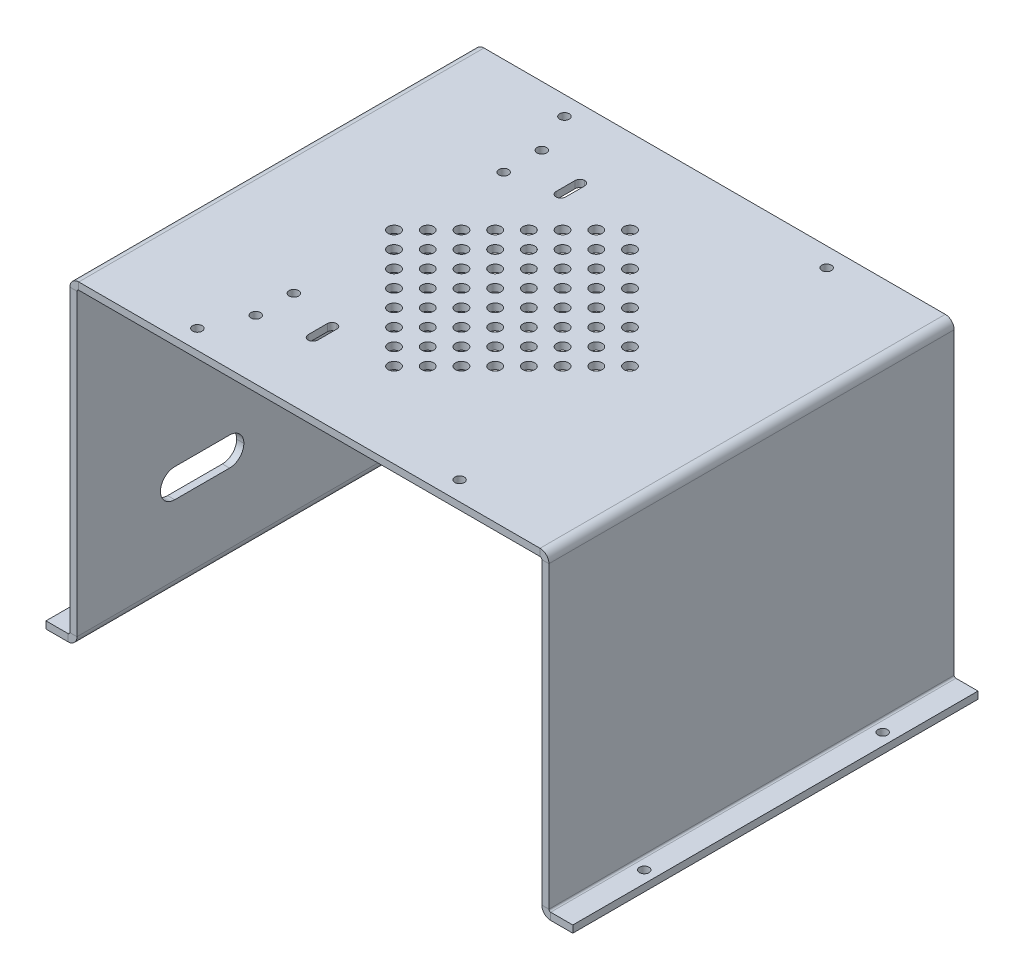
SolidWorks part; units mm, degrees
note: The reader was unsure of these and kept them because the rebuilt part matched: flange length of "边线-法兰1", "边线-法兰2".
ref_plane "前视基准面" through (0, 0, 0) normal (0, 0, 1) x (1, 0, 0)
ref_plane "上视基准面" through (0, 0, 0) normal (0, 1, 0) x (1, 0, 0)
ref_plane "右视基准面" through (0, 0, 0) normal (1, 0, 0) x (0, 0, -1)
sketch "草图1" plane through (0, 0, 0) normal (0, 1, 0) x (1, 0, 0)
  line L1 (-97.5, -85) -> (97.5, -85)
  line L2 (-97.5, -85) -> (-97.5, 85)
  line L3 (-97.5, 85) -> (97.5, 85)
  line L4 (97.5, -85) -> (97.5, 85)
  line L5 (-97.5, -85) -> (97.5, 85) construction
  line L6 (-97.5, 85) -> (97.5, -85) construction
  point P0 (0, 0)
  dimension "D1" = 170
  dimension "D2" = 195
base flange "基体-法兰1" sketch "草图1" thickness 3 reverse thickness direction no parameters "D1"=0.7366
sketch "草图6" plane through (0, 0, 0) normal (0, 1, 0) x (1, 0, 0)
  line L0 (-97.5, -85) -> (97.5, -85) construction
  line L1 (0, 85) -> (0, -85) construction
  line L2 (97.5, 85) -> (-97.5, 85) construction
  line L3 (-97.5, 0) -> (97.5, 0) construction
  line L4 (-97.5, 85) -> (-97.5, -85) construction
  line L5 (97.5, -85) -> (97.5, 85) construction
  line L6 (-25.5, -58) -> (-29.5, -58)
  line L11 (-25.5, 46) -> (-29.5, 46)
  line L12 (-25.5, 46) -> (-25.5, 58)
  line L13 (-25.5, 58) -> (-29.5, 58)
  line L14 (-29.5, 46) -> (-29.5, 58)
  line L15 (-25.5, 46) -> (-29.5, 58) construction
  line L16 (-25.5, 58) -> (-29.5, 46) construction
  line L17 (-29.5, -46) -> (-29.5, -58)
  line L18 (-25.5, -46) -> (-29.5, -46)
  line L19 (-25.5, -46) -> (-25.5, -58)
  line L21 (-35.5, 40) -> (-83.5, 40) construction
  line L22 (-35.5, 40) -> (-35.5, 64) construction
  line L23 (-35.5, 64) -> (-83.5, 64) construction
  line L24 (-83.5, 40) -> (-83.5, 64) construction
  line L25 (-35.5, 40) -> (-83.5, 64) construction
  line L26 (-35.5, 64) -> (-83.5, 40) construction
  circle A0 centre (-55, -77) radius 2
  circle A1 centre (55, -77) radius 2
  circle A4 centre (55, 77) radius 2
  circle A5 centre (-55, 77) radius 2
  circle A6 centre (-47.5, 60) radius 2
  circle A7 centre (-47.5, 44) radius 2
  circle A10 centre (-47.5, -44) radius 2
  circle A11 centre (-47.5, -60) radius 2
  circle A12 centre (0, 49.4975) radius 2.5
  circle A13 centre (-7.0711, 42.4264) radius 2.5
  circle A14 centre (-14.1421, 35.3553) radius 2.5
  circle A15 centre (-21.2132, 28.2843) radius 2.5
  circle A16 centre (-28.2843, 21.2132) radius 2.5
  circle A17 centre (-35.3553, 14.1421) radius 2.5
  circle A18 centre (-42.4264, 7.0711) radius 2.5
  circle A19 centre (-49.4975, 0) radius 2.5
  circle A20 centre (0, 35.3553) radius 2.5
  circle A21 centre (-7.0711, 28.2843) radius 2.5
  circle A22 centre (-14.1421, 21.2132) radius 2.5
  circle A23 centre (-21.2132, 14.1421) radius 2.5
  circle A24 centre (-28.2843, 7.0711) radius 2.5
  circle A25 centre (-35.3553, 0) radius 2.5
  circle A26 centre (-42.4264, -7.0711) radius 2.5
  circle A27 centre (7.0711, 28.2843) radius 2.5
  circle A28 centre (0, 21.2132) radius 2.5
  circle A29 centre (-7.0711, 14.1421) radius 2.5
  circle A30 centre (-14.1421, 7.0711) radius 2.5
  circle A31 centre (-21.2132, 0) radius 2.5
  circle A32 centre (-28.2843, -7.0711) radius 2.5
  circle A33 centre (-35.3553, -14.1421) radius 2.5
  circle A34 centre (14.1421, 21.2132) radius 2.5
  circle A35 centre (7.0711, 14.1421) radius 2.5
  circle A36 centre (0, 7.0711) radius 2.5
  circle A37 centre (-7.0711, 0) radius 2.5
  circle A38 centre (-14.1421, -7.0711) radius 2.5
  circle A39 centre (-21.2132, -14.1421) radius 2.5
  circle A40 centre (-28.2843, -21.2132) radius 2.5
  circle A41 centre (21.2132, 14.1421) radius 2.5
  circle A42 centre (14.1421, 7.0711) radius 2.5
  circle A43 centre (7.0711, 0) radius 2.5
  circle A44 centre (0, -7.0711) radius 2.5
  circle A45 centre (-7.0711, -14.1421) radius 2.5
  circle A46 centre (-14.1421, -21.2132) radius 2.5
  circle A47 centre (-21.2132, -28.2843) radius 2.5
  circle A48 centre (28.2843, 7.0711) radius 2.5
  circle A49 centre (21.2132, 0) radius 2.5
  circle A50 centre (14.1421, -7.0711) radius 2.5
  circle A51 centre (7.0711, -14.1421) radius 2.5
  circle A52 centre (0, -21.2132) radius 2.5
  circle A53 centre (-7.0711, -28.2843) radius 2.5
  circle A54 centre (-14.1421, -35.3553) radius 2.5
  circle A55 centre (35.3553, 0) radius 2.5
  circle A56 centre (28.2843, -7.0711) radius 2.5
  circle A57 centre (21.2132, -14.1421) radius 2.5
  circle A58 centre (14.1421, -21.2132) radius 2.5
  circle A59 centre (7.0711, -28.2843) radius 2.5
  circle A60 centre (0, -35.3553) radius 2.5
  circle A61 centre (-7.0711, -42.4264) radius 2.5
  circle A62 centre (42.4264, -7.0711) radius 2.5
  circle A63 centre (35.3553, -14.1421) radius 2.5
  circle A64 centre (28.2843, -21.2132) radius 2.5
  circle A65 centre (21.2132, -28.2843) radius 2.5
  circle A66 centre (14.1421, -35.3553) radius 2.5
  circle A67 centre (7.0711, -42.4264) radius 2.5
  circle A68 centre (0, -49.4975) radius 2.5
  circle A69 centre (7.0711, 42.4264) radius 2.5
  circle A70 centre (14.1421, 35.3553) radius 2.5
  circle A71 centre (21.2132, 28.2843) radius 2.5
  circle A72 centre (28.2843, 21.2132) radius 2.5
  circle A73 centre (35.3553, 14.1421) radius 2.5
  circle A74 centre (42.4264, 7.0711) radius 2.5
  circle A75 centre (49.4975, 0) radius 2.5
  point P28 (-27.5, 52)
  point P37 (-59.5, 52)
  point P42 (0, 0)
  dimension "D1" = 4
  dimension "D4" = 4
  dimension "D15" = 5
  dimension "D2" = 8
  dimension "D3" = 110
  dimension "D5" = 2
  dimension "D6" = 50
  dimension "D7" = 25
  dimension "D8" = 4
  dimension "D9" = 12
  dimension "D10" = 8
  dimension "D11" = 20
  dimension "D12" = 48
  dimension "D13" = 24
  dimension "D14" = 12
  dimension "D19" = 8
  dimension "D20" = 8
extrude "切除-拉伸1" cut sketch "草图6" against normal up to next (3 mm away) normal cut yes
edge flange "边线-法兰1" sketch "草图9" flange angle 90 flange length 130 flange position material outside bend radius 0.7366 thickness 3 relief rectangular parameters "D6"=10
sketch "草图9" plane through (-97.5, -3, 0) normal (-1, 0, 0) x (0, 0, -1)
  line L0 (85, 0) -> (-85, 0) construction
  line L1 (85, 0) -> (-85, 0)
  line L2 (-85, 0) -> (-85, 130)
  line L3 (-85, 130) -> (85, 130)
  line L4 (85, 130) -> (85, 0)
bend "边线折弯1" bend radius 0.7366 bend angle 90 parameters "D5"=1
edge flange "边线-法兰2" sketch "草图12" flange angle 90 flange length 10 flange position material inside bend radius 0.7366 thickness 3 relief rectangular parameters "D6"=10
sketch "草图12" plane through (-100.5, -133, 0) normal (0, -1, 0) x (0, 0, 1)
  line L0 (-85, 0) -> (85, 0) construction
  line L1 (-85, 0) -> (85, 0)
  line L2 (-85, 0) -> (-85, 10)
  line L3 (-85, 10) -> (85, 10)
  line L4 (85, 10) -> (85, 0)
bend "边线折弯2" bend radius 0.7366 bend angle 90 parameters "D5"=2
sketch "草图13" plane through (0, -133, 0) normal (0, -1, 0) x (1, 0, 0)
  line L0 (-110.5, 85) -> (-110.5, -85) construction
  line L1 (-110.5, 0) -> (-101.2366, 0) construction
  line L2 (-101.2366, 85) -> (-101.2366, -85) construction
  circle A0 centre (-105.5, 50) radius 2
  circle A1 centre (-105.5, -50) radius 2
  dimension "D1" = 4
  dimension "D2" = 5
  dimension "D3" = 100
extrude "切除-拉伸2" cut sketch "草图13" against normal up to next normal cut yes
mirror "镜向1" about plane through (0, 0, 0) normal (1, 0, 0) of "切除-拉伸2", "边线-法兰2", "边线-法兰1"
bend "镜向折弯1" bend radius 0.7366 bend angle 90 parameters "D5"=3
bend "镜向折弯2" bend radius 0.7366 bend angle 90 parameters "D5"=4
sketch "草图14" plane through (-100.5, 0, 0) normal (-1, 0, 0) x (0, 0, 1)
  line L0 (0, -3.7366) -> (0, -129.2634) construction
  line L1 (-85, -3.7366) -> (85, -3.7366) construction
  line L2 (85, -129.2634) -> (-85, -129.2634) construction
  line L3 (-85, -130) -> (85, -130) construction
  line L4 (-50, -88) -> (-15, -88)
  line L5 (-50, -88) -> (-50, -100)
  line L6 (-50, -100) -> (-15, -100)
  line L7 (-15, -88) -> (-15, -100)
  line L8 (50, -100) -> (15, -100)
  line L9 (15, -88) -> (15, -100)
  line L10 (50, -88) -> (15, -88)
  line L11 (50, -88) -> (50, -100)
  dimension "D1" = 35
  dimension "D2" = 12
  dimension "D3" = 30
  dimension "D4" = 15
extrude "切除-拉伸3" cut sketch "草图14" against normal up to next normal cut yes
fillet "圆角1" radius 6 8 edges at (-99, -100, 50) (-99, -88, 50) (-99, -88, 15) (-99, -100, 15) (-99, -88, -15) (-99, -100, -15) (-99, -100, -50) (-99, -88, -50)
fillet "圆角2" radius 2 8 edges at (-25.5, -1.5, 58) (-29.5, -1.5, 58) (-29.5, -1.5, 46) (-25.5, -1.5, 46) (-25.5, -1.5, -58) (-25.5, -1.5, -46) (-29.5, -1.5, -46) (-29.5, -1.5, -58)
sketch "折弯-线1" plane through (0, 0, 0) normal (0, 1, 0) x (1, 0, 0)
sketch "边界框1" plane through (0, 0, 0) normal (0, 1, 0) x (1, 0, 0)
sheet metal parameters "钣金6" thickness 3 parameters "D1"=0.7366
flat pattern "平板型式6" [suppressed]
sketch "折弯-线2" plane through (0, 0, 0) normal (0, 1, 0) x (1, 0, 0)
sketch "边界框2" [suppressed] plane through (0, 0, 0) normal (0, 1, 0) x (1, 0, 0)
sheet metal parameters "钣金7" thickness 3 parameters "D1"=0.7366
flat pattern "平板型式6"
sketch "折弯-线2" plane through (0, 0, 0) normal (0, 1, 0) x (1, 0, 0)
sketch "边界框2" [suppressed] plane through (0, 0, 0) normal (0, 1, 0) x (1, 0, 0)
sheet metal parameters "钣金8" thickness 3 parameters "D1"=0.7366
flat pattern "平板型式6" [suppressed]
sketch "折弯-线2" plane through (0, 0, 0) normal (0, 1, 0) x (1, 0, 0)
sketch "边界框2" [suppressed] plane through (0, 0, 0) normal (0, 1, 0) x (1, 0, 0)
bend of the flat pattern "展平-<边线折弯1>1"
sheet metal parameters "钣金9" thickness 3 parameters "D1"=0.7366
flat pattern "平板型式6" [suppressed]
sketch "折弯-线2" plane through (0, 0, 0) normal (0, 1, 0) x (1, 0, 0)
sketch "边界框2" [suppressed] plane through (0, 0, 0) normal (0, 1, 0) x (1, 0, 0)
bend of the flat pattern "展平-<边线折弯1>1"
bend of the flat pattern "展平-<边线折弯2>1"
sheet metal parameters "钣金10" thickness 3 parameters "D1"=0.7366
flat pattern "平板型式6" [suppressed]
sketch "折弯-线2" plane through (0, 0, 0) normal (0, 1, 0) x (1, 0, 0)
sketch "边界框2" [suppressed] plane through (0, 0, 0) normal (0, 1, 0) x (1, 0, 0)
bend of the flat pattern "展平-<边线折弯1>1"
bend of the flat pattern "展平-<边线折弯2>1"
bend of the flat pattern "展平-<镜向折弯1>1"
bend of the flat pattern "展平-<镜向折弯2>1"
sheet metal parameters "钣金11" thickness 3 parameters "D1"=0.7366
flat pattern "平板型式6" [suppressed]
sketch "折弯-线2" plane through (0, 0, 0) normal (0, 1, 0) x (1, 0, 0)
sketch "边界框2" [suppressed] plane through (0, 0, 0) normal (0, 1, 0) x (1, 0, 0)
bend of the flat pattern "展平-<边线折弯1>1"
bend of the flat pattern "展平-<边线折弯2>1"
sheet metal parameters "钣金12" thickness 3 parameters "D1"=0.7366
flat pattern "平板型式6" [suppressed]
sketch "折弯-线2" plane through (0, 0, 0) normal (0, 1, 0) x (1, 0, 0)
sketch "边界框2" [suppressed] plane through (0, 0, 0) normal (0, 1, 0) x (1, 0, 0)
bend of the flat pattern "展平-<边线折弯1>1"
bend of the flat pattern "展平-<边线折弯2>1"
bend of the flat pattern "展平-<镜向折弯1>1"
bend of the flat pattern "展平-<镜向折弯2>1"
